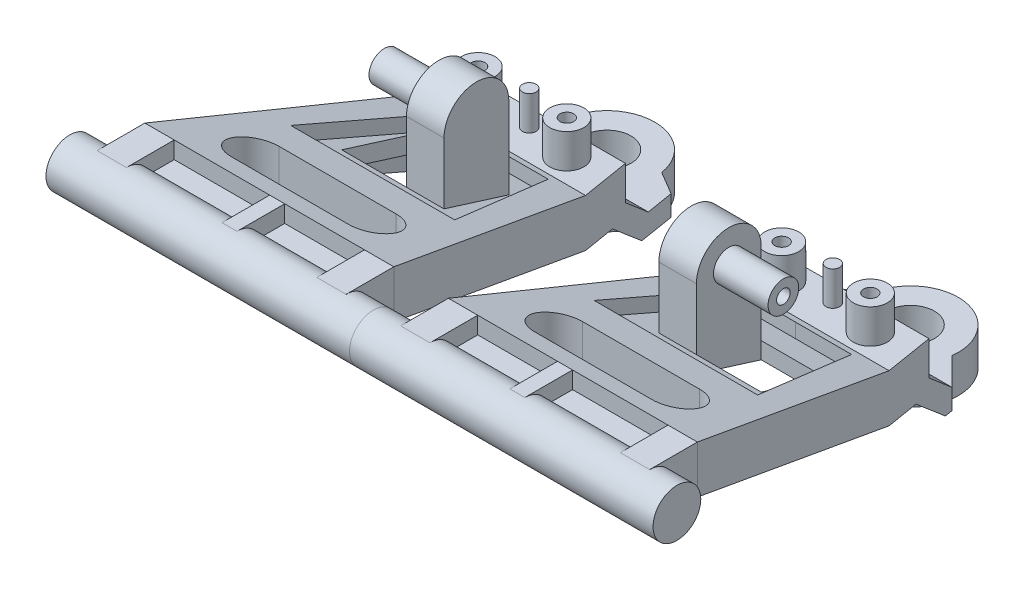
SolidWorks part; units mm, degrees
note: The reader was unsure of these and kept them because the rebuilt part matched: shared geometry of "Sketch13<3>", "Sketch13<4>".
ref_plane "Front Plane" through (0, 0, 0) normal (0, 0, 1) x (1, 0, 0)
ref_plane "Top Plane" through (0, 0, 0) normal (0, 1, 0) x (1, 0, 0)
ref_plane "Right Plane" through (0, 0, 0) normal (1, 0, 0) x (0, 0, -1)
sketch "Sketch1" plane through (0, 0, 0) normal (1, 0, 0) x (0, 0, -1)
  line L0 (7, -3.5) -> (40.6071, -14)
  line L1 (40.6071, -14) -> (45.75, -18.5)
  line L2 (45.75, -18.5) -> (49.75, -18.5)
  line L4 (49.75, -18.5) -> (63.5, -18.5)
  line L5 (63.5, -18.5) -> (63.5, -15.5)
  line L6 (63.5, -15.5) -> (51.6071, -15.5)
  line L7 (51.6071, -15.5) -> (47.6071, -12)
  line L8 (47.6071, -12) -> (47.6071, -7)
  line L9 (47.6071, -7) -> (40.6071, -7)
  line L10 (40.6071, -7) -> (7, 3.5)
  line L11 (0, 3.5) -> (7, 3.5)
  line L12 (0, -3.5) -> (7, -3.5)
  arc A0 (0, 3.5) -> (0, -3.5) centre (0, 0) ccw
  dimension "D1" = 7
  dimension "D2" = 5
  dimension "D7" = 63.5
  dimension "D4" = 18.5
  dimension "D3" = 13.75
  dimension "D5" = 3
  dimension "D6" = 4
  dimension "D9" = 7
  dimension "D10" = 7
  dimension "D11" = 7
  dimension "D12" = 4
extrude "Boss-Extrude1" add sketch "Sketch1" along normal blind 36.5 contours L10 L11 A0 L12 L0 L1 L2 L4 L5 L6 L7 L8 L9
sketch "Sketch2" plane through (0, 0, 0) normal (0, 1, 0) x (1, 0, 0)
  line L0 (18.25, -3.5) -> (18.25, 63.5) construction
  line L1 (0, -3.5) -> (36.5, -3.5) construction
  line L2 (36.5, 63.5) -> (36.5, 51.6071) construction
  line L3 (25.1928, 55.6071) -> (29.1928, 51.6071)
  line L4 (36.5, 51.6071) -> (0, 51.6071) construction
  line L5 (29.1928, 51.6071) -> (36.5, 7)
  line L6 (36.5, 7) -> (46.5, 7)
  line L7 (46.5, 7) -> (46.5, 73.5)
  line L8 (46.5, 73.5) -> (-10, 73.5)
  line L9 (-10, 7) -> (-10, 73.5)
  line L10 (0, 7) -> (-10, 7)
  line L11 (7.9624, 55.6071) -> (0, 7)
  line L12 (11.3381, 57.6071) -> (7.9624, 55.6071)
  line L13 (36.5, 63.5) -> (0, 63.5) construction
  line L14 (9.6781, 13.5) -> (26.8219, 13.5) construction
  line L15 (9.6781, 17) -> (26.8219, 17)
  line L16 (9.6781, 10) -> (26.8219, 10)
  line L17 (36.5, 7) -> (0, 7) construction
  line L18 (36.5, 47.6071) -> (0, 47.6071) construction
  line L19 (17.25, 35.6071) -> (26.75, 35.6071)
  line L20 (17.25, 35.6071) -> (17.25, 26.1071)
  line L21 (17.25, 26.1071) -> (26.75, 26.1071)
  line L22 (26.75, 35.6071) -> (26.75, 26.1071)
  arc A0 (25.1928, 55.6071) -> (11.3381, 57.6071) centre (18.25, 56.5) ccw
  circle A1 centre (18.25, 56.5) radius 3.5
  arc A2 (9.6781, 17) -> (9.6781, 10) centre (9.6781, 13.5) ccw
  arc A3 (26.8219, 10) -> (26.8219, 17) centre (26.8219, 13.5) ccw
  point P20 (18.25, 73.5)
  point P23 (18.25, 13.5)
  dimension "D1" = 14
  dimension "D8" = 7
  dimension "D9" = 3.5
  dimension "D2" = 4
  dimension "D3" = 4
  dimension "D4" = 9.303
  dimension "D5" = 2
  dimension "D6" = 10
  dimension "D7" = 10
  dimension "D10" = 8.5
  dimension "D11" = 3
  dimension "D12" = 1
  dimension "D13" = 12
  dimension "D14" = 9.5
  dimension "D15" = 9.5
extrude "Cut-Extrude1" cut sketch "Sketch2" against normal blind 36.5 and the other way through all
sketch "Sketch5" plane through (0, 3.5, 0) normal (0, 1, 0) x (1, 0, 0)
  line L0 (36.5, 0) -> (0, 0) construction
  line L1 (4.3, 0) -> (16, 0)
  line L2 (4.3, 0) -> (4.3, 7)
  line L3 (4.3, 7) -> (16, 7)
  line L4 (16, 0) -> (16, 7)
  line L5 (36.5, 0) -> (36.5, 7) construction
  line L6 (18.2, 7) -> (32.2, 7)
  line L7 (18.2, 7) -> (18.2, 0)
  line L8 (18.2, 0) -> (32.2, 0)
  line L9 (32.2, 7) -> (32.2, 0)
  line L10 (0, 0) -> (0, 7) construction
  line L12 (9.6781, 10) -> (26.8219, 10) construction
  dimension "D1" = 4.3
  dimension "D2" = 4.3
  dimension "D3" = 3
  dimension "D4" = 2.2
  dimension "D5" = 14
extrude "Cut-Extrude2" cut sketch "Sketch5" against normal blind 2.5
sketch "Sketch6" plane through (0, -3.5, 0) normal (0, -1, 0) x (1, 0, 0)
  line L4 (18.2, -7) -> (32.2, -7)
  line L5 (32.2, -7) -> (32.2, 0)
  line L6 (32.2, 0) -> (18.2, 0)
  line L7 (18.2, 0) -> (18.2, -7)
  line L8 (18.2, -7) -> (32.2, -7)
  line L9 (32.2, -7) -> (32.2, 0)
  line L10 (32.2, 0) -> (18.2, 0)
  line L11 (18.2, 0) -> (18.2, -7)
  line L12 (16, 0) -> (4.3, 0)
  line L13 (16, -7) -> (16, 0)
  line L14 (4.3, -7) -> (16, -7)
  line L15 (4.3, 0) -> (4.3, -7)
  line L16 (16, 0) -> (4.3, 0)
  line L17 (16, -7) -> (16, 0)
  line L18 (4.3, -7) -> (16, -7)
  line L19 (4.3, 0) -> (4.3, -7)
  dimension "D1" = 0
  dimension "D2" = 0
extrude "Cut-Extrude3" cut sketch "Sketch6" against normal blind 2.5
sketch "Sketch3" plane through (36.5, 0, 0) normal (1, 0, 0) x (0, 0, -1)
  circle A0 centre (0, 0) radius 3.5
  dimension "D1" = 7
extrude "Boss-Extrude2" add sketch "Sketch3" along normal blind 4 and the other way blind 40.5 contours A0
sketch "Sketch7" plane through (0, 0, 0) normal (0, 1, 0) x (1, 0, 0)
  line L0 (18.2225, 22.1071) -> (30.2225, 22.1071)
  line L1 (30.2225, 22.1071) -> (26.4985, 39.6071)
  line L2 (26.4985, 39.6071) -> (18.2485, 39.6071)
  line L4 (18.2, 7) -> (18.25, 40.6071) construction
  line L5 (30.9948, 40.6071) -> (5.5052, 40.6071) construction
  line L6 (9.9985, 39.6317) -> (18.2485, 39.6071)
  line L7 (6.2225, 22.1428) -> (9.9985, 39.6317)
  line L8 (18.2225, 22.1071) -> (6.2225, 22.1428)
  dimension "D1" = 8.25
  dimension "D2" = 12
  dimension "D3" = 17.5
  dimension "D4" = 1
extrude "Cut-Extrude4" cut sketch "Sketch7" against normal offset from surface (8.8061 mm away) 4.6667
ref_plane "Plane1" through (0, -18.5, 0) normal (0, 1, 0) x (1, 0, 0)
sketch "Sketch8" plane through (0, -18.5, 0) normal (0, 1, 0) x (1, 0, 0)
  line L6 (18.2225, 22.1071) -> (30.2225, 22.1071)
  line L7 (30.2225, 22.1071) -> (26.4985, 39.6071)
  line L8 (26.4985, 39.6071) -> (18.2485, 39.6071)
  line L9 (18.2485, 39.6071) -> (9.9985, 39.6317)
  line L10 (9.9985, 39.6317) -> (6.2225, 22.1428)
  line L11 (6.2225, 22.1428) -> (18.2225, 22.1071)
  line L12 (18.2225, 22.1071) -> (30.2225, 22.1071)
  line L13 (30.2225, 22.1071) -> (26.4985, 39.6071)
  line L14 (26.4985, 39.6071) -> (18.2485, 39.6071)
  line L15 (18.2485, 39.6071) -> (9.9985, 39.6317)
  line L16 (9.9985, 39.6317) -> (6.2225, 22.1428)
  line L17 (6.2225, 22.1428) -> (18.2225, 22.1071)
  dimension "D1" = 0
extrude "Cut-Extrude5" cut sketch "Sketch8" along normal offset from surface (7.2493 mm away) 2.3333
sketch "Sketch9" plane through (17.25, 0, 0) normal (1, 0, 0) x (0, 0, -1)
  line L0 (26.1071, -4.5806) -> (26.1071, 4.4194)
  line L1 (35.6071, 4.4194) -> (35.6071, -7.5487)
  line L2 (26.1071, -4.5806) -> (35.6071, -7.5487)
  line L3 (35.6071, -7.5487) -> (26.1071, -4.5806) construction
  arc A0 (26.1071, 4.4194) -> (35.6071, 4.4194) centre (30.8571, 4.4194) cw
  dimension "D1" = 9
extrude "Boss-Extrude3" add sketch "Sketch9" against normal blind 5.5
sketch "Sketch10" plane through (17.25, 0, 0) normal (1, 0, 0) x (0, 0, -1)
  circle A0 centre (30.8571, 4.4194) radius 2.25
  circle A1 centre (30.8571, 4.4194) radius 1
  dimension "D1" = 4.5
  dimension "D2" = 2
extrude "Boss-Extrude4" add sketch "Sketch10" along normal blind 8
sketch "Sketch11" plane through (0, -7, 0) normal (0, 1, 0) x (1, 0, 0)
  line L0 (18.25, 47.6071) -> (18.25, 40.6071) construction
  line L1 (29.8481, 47.6071) -> (6.6519, 47.6071) construction
  line L2 (30.9948, 40.6071) -> (5.5052, 40.6071) construction
  line L3 (29.8481, 47.6071) -> (6.6519, 47.6071) construction
  line L4 (11.75, 44.1071) -> (18.25, 44.1071) construction
  circle A0 centre (11.75, 44.1071) radius 2.5
  circle A1 centre (18.25, 45.1071) radius 1
  circle A2 centre (11.75, 44.1071) radius 1
  circle A3 centre (24.75, 44.1071) radius 1
  circle A4 centre (24.75, 44.1071) radius 2.5
  dimension "D1" = 2
  dimension "D2" = 5
  dimension "D3" = 2.5
  dimension "D5" = 2
  dimension "D4" = 6.5
extrude "Boss-Extrude5" add sketch "Sketch11" along normal blind 5
sketch "Sketch13" plane through (0, 0, 0) normal (1, 0, 0) x (0, 0, -1)
  line L0 (51.6071, -15.5) -> (47.6071, -12) construction
  line L1 (55.6071, -15.5) -> (51.6071, -15.5) construction
  line L2 (51.6071, -15.5) -> (47.6071, -12) construction
  line L3 (55.6071, -15.5) -> (51.6071, -15.5) construction
  line L5 (53.9085, -21.5) -> (45.3371, -14)
  line L6 (45.75, -18.5) -> (51.6071, -18.5) construction
  line L7 (40.6071, -14) -> (45.3371, -14)
  line L8 (40.6071, -14) -> (40.6071, -21.5)
  line L9 (40.6071, -21.5) -> (53.9085, -21.5)
  dimension "D2" = 3
  dimension "D1" = 3
extrude "Cut-Extrude7" cut sketch "Sketch13" along normal blind 12 contours L9 L5 L7 L8
extrude "Cut-Extrude8" cut sketch "Sketch13<3>" along normal blind 8.25 from offset 14.5
sketch "Sketch13<3>" plane through (0, 0, 0) normal (1, 0, 0) x (0, 0, -1) same geometry as "Sketch13"
extrude "Cut-Extrude9" cut sketch "Sketch13<4>" along normal blind 8 from offset 25.25
sketch "Sketch13<4>" plane through (0, 0, 0) normal (1, 0, 0) x (0, 0, -1) same geometry as "Sketch13"
sketch "Sketch14" plane through (0, -18.5, 0) normal (0, -1, 0) x (1, 0, 0)
  circle A0 centre (18.25, -56.5) radius 7
  circle A1 centre (18.25, -56.5) radius 3.5
  dimension "D1" = 14
  dimension "D2" = 7
extrude "Boss-Extrude6" add sketch "Sketch14" along normal blind 2.5 and the other way up to surface other way up to face at (27.5244, -16.25, -47.9085)
mirror "Mirror2" about plane through (-4, 0, 0) normal (1, 0, 0) of bodies 115
